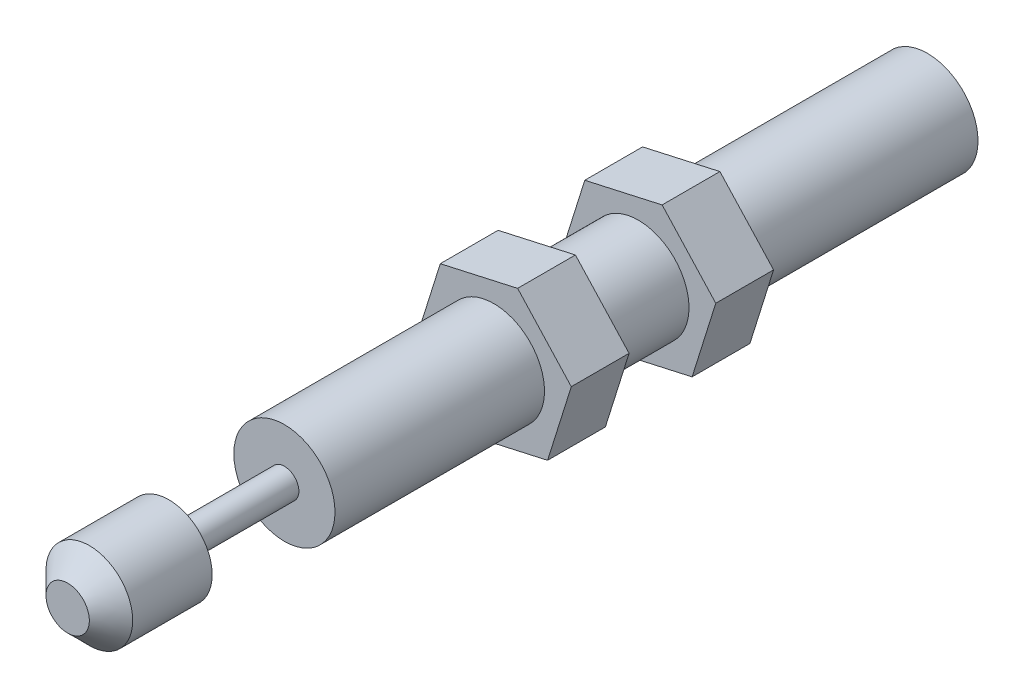
SolidWorks part; units mm, degrees
ref_plane "前视基准面" through (0, 0, 0) normal (0, 0, 1) x (1, 0, 0)
ref_plane "上视基准面" through (0, 0, 0) normal (0, 1, 0) x (1, 0, 0)
ref_plane "右视基准面" through (0, 0, 0) normal (1, 0, 0) x (0, 0, -1)
sketch "草图1" plane through (0, 0, 0) normal (0, 0, 1) x (1, 0, 0)
  circle A0 centre (0, 0) radius 7
  dimension "D1" = 14
extrude "凸台-拉伸1" add sketch "草图1" along normal blind 89
sketch "草图2" plane through (0, 0, 89) normal (0, 0, 1) x (1, 0, 0)
  circle A0 centre (0, 0) radius 2
  dimension "D1" = 4
extrude "凸台-拉伸2" add sketch "草图2" along normal blind 16
sketch "草图3" plane through (0, 0, 105) normal (0, 0, 1) x (1, 0, 0)
  circle A0 centre (0, 0) radius 6
  dimension "D1" = 12
extrude "凸台-拉伸3" add sketch "草图3" along normal blind 14
chamfer "倒角1" distance 3 angle 45 1 edges at (6, 0, 119)
ref_plane "基准面1" through (0, 0, 40) normal (0, 0, -1) x (-1, 0, 0)
sketch "草图4" plane through (0, 0, 40) normal (0, 0, -1) x (-1, 0, 0)
  line L1 (-3.2778, 10.4685) -> (-10.7049, 2.3956)
  line L2 (-10.7049, 2.3956) -> (-7.4271, -8.0729)
  line L3 (-7.4271, -8.0729) -> (3.2778, -10.4685)
  line L4 (3.2778, -10.4685) -> (10.7049, -2.3956)
  line L5 (10.7049, -2.3956) -> (7.4271, 8.0729)
  line L6 (7.4271, 8.0729) -> (-3.2778, 10.4685)
  circle A0 centre (0, 0) radius 9.5 construction
  dimension "D1" = 19
extrude "凸台-拉伸4" add sketch "草图4" along normal blind 8
ref_axis "基准轴1" through (0, 0, 89) along (0, 0, -1)
pattern_linear "阵列(线性)1" count 2 spacing 20 along (0, 0, 1) of "凸台-拉伸4"
